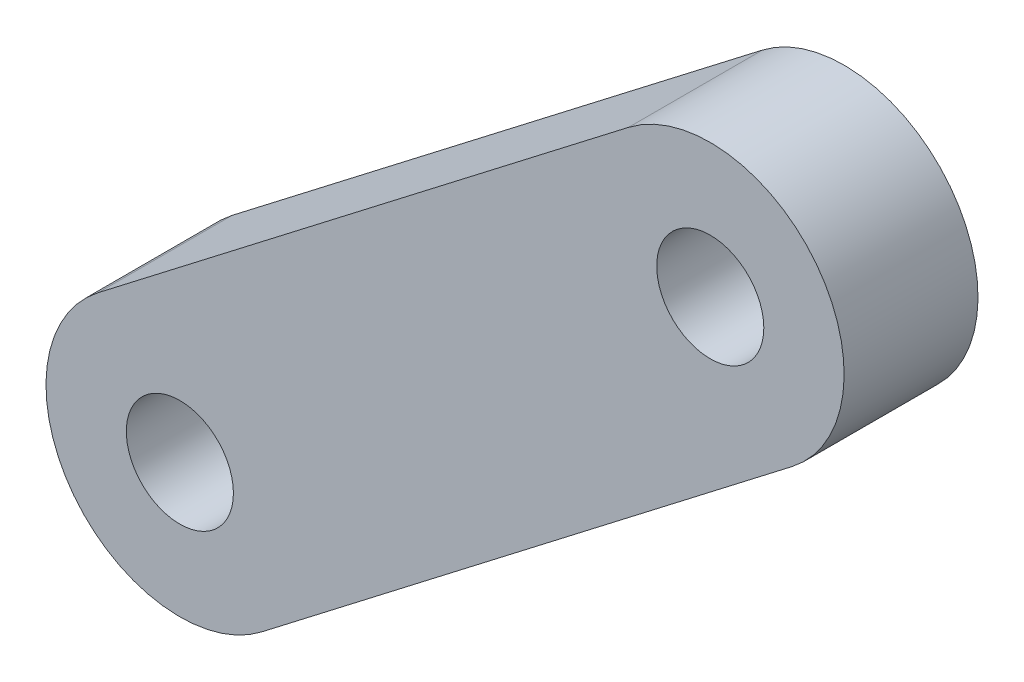
SolidWorks part; units mm, degrees
ref_plane "Front Plane" through (0, 0, 0) normal (0, 0, 1) x (1, 0, 0)
ref_plane "Top Plane" through (0, 0, 0) normal (0, 1, 0) x (1, 0, 0)
ref_plane "Right Plane" through (0, 0, 0) normal (1, 0, 0) x (0, 0, -1)
sketch "Sketch1" plane through (0, 0, 0) normal (0, 0, 1) x (0.9998, -0.022, 0)
  line L0 (-41.8829, 111.4723) -> (-17.0715, 91.626) construction
  line L1 (-1.7639, 79.3817) -> (-1.7639, 99.3817) construction
  line L2 (-1.7639, 99.3817) -> (-51.7712, 99.3817) construction
  line L3 (-46.2352, 83.6971) -> (-26.7675, 99.3817) construction
  line L4 (-46.2352, 83.6971) -> (-49.3722, 87.5906) construction
  line L5 (-49.3722, 87.5906) -> (-43.0983, 79.8035) construction
  line L6 (-49.3722, 87.5906) -> (-29.9044, 103.2753)
  line L7 (-43.0983, 79.8035) -> (-23.6306, 95.4882)
  line L8 (-29.9044, 103.2753) -> (-23.6306, 95.4882) construction
  circle A0 centre (-1.7639, 79.3817) radius 2.5 construction
  circle A1 centre (-1.7639, 79.3817) radius 2.5 construction
  circle A3 centre (-26.7675, 99.3817) radius 2
  arc A4 (-22.8629, 96.2585) -> (-30.6611, 96.2448) centre (-26.7675, 99.3817) ccw
  circle A5 centre (-46.2352, 83.6971) radius 2 construction
  circle A6 centre (-46.2352, 83.6971) radius 2
  arc A7 (-49.3722, 87.5906) -> (-43.0983, 79.8035) centre (-46.2352, 83.6971) ccw
  arc A8 (-23.6306, 95.4882) -> (-29.9044, 103.2753) centre (-26.7675, 99.3817) ccw
  point P18 (-26.7675, 99.3817)
  dimension "D1" = 5
  dimension "D2" = 5
  dimension "D4" = 4
  dimension "D5" = 4
  dimension "D6" = 10
  dimension "D3" = 20
  dimension "D7" = 25
extrude "Boss-Extrude1" add sketch "Sketch1" along normal blind 5 contours L7 A8 L6 A7 A3 A6 region at (-34.4759, 92.3213, 0)
sketch "Sketch2" plane through (0, 0, 0) normal (0, 0, -1) x (-1, 0, 0)
  circle A0 centre (44.3801, 84.6953) radius 2
extrude "Boss-Extrude2" add sketch "Sketch2" along normal blind 5 separate body
move or copy body "Body-Move/Copy1" [suppressed] bodies to move or copy 101 102
